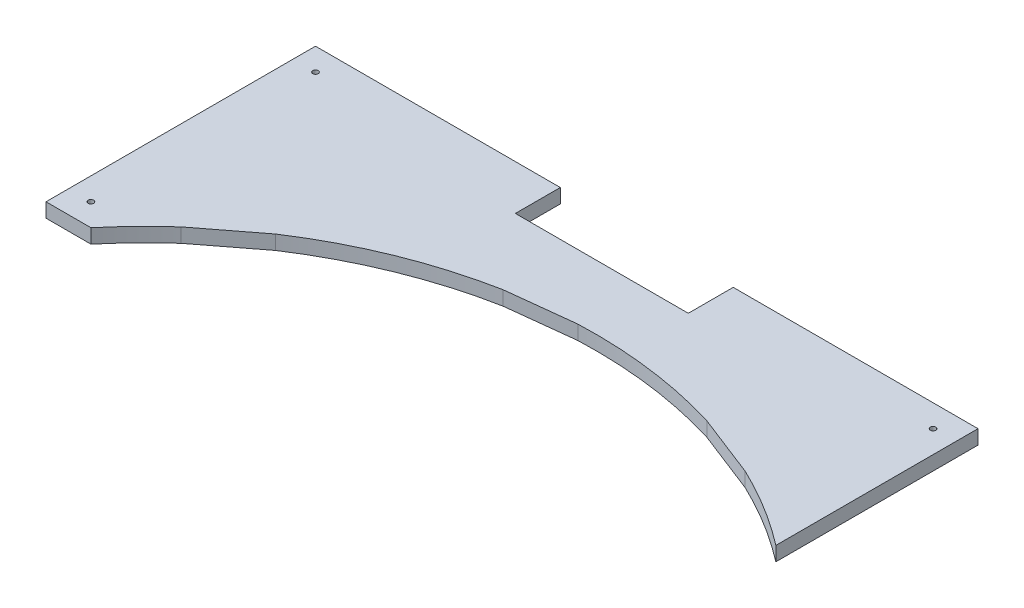
SolidWorks part; units mm, degrees
material "Balsa"
ref_plane "Front Plane" through (0, 0, 0) normal (0, 0, 1) x (1, 0, 0)
ref_plane "Top Plane" through (0, 0, 0) normal (0, 1, 0) x (1, 0, 0)
ref_plane "Right Plane" through (0, 0, 0) normal (1, 0, 0) x (0, 0, -1)
sketch "Sketch1" plane through (0, 0, 0) normal (0, 1, 0) x (1, 0, 0)
  line L0 (20, 0) -> (0, 0)
  line L5 (0, 0) -> (0, 120)
  line L6 (0, 120) -> (295, 120)
  line L7 (295, 120) -> (295, 30)
  line L17 (39.7609, 20.3984) -> (63.5533, 38.6789)
  line L18 (135.6372, 67.8391) -> (165.645, 71.2503)
  line L19 (231.6087, 62.6625) -> (259.6066, 51.7472)
  arc A0 (20, 0) -> (39.7609, 20.3984) centre (173.1663, -128.6082) cw
  arc A1 (63.5533, 38.6789) -> (135.6372, 67.8391) centre (173.1663, -128.6082) cw
  arc A2 (165.645, 71.2503) -> (231.6087, 62.6625) centre (173.1663, -128.6082) cw
  arc A3 (259.6066, 51.7472) -> (295, 30) centre (173.1663, -128.6082) cw
  circle A4 centre (10, 110) radius 1.225
  circle A5 centre (10, 10) radius 1.225
  circle A6 centre (285, 110) radius 1.225
  dimension "D5" = 200
  dimension "D8" = 2.45
  dimension "D11" = 2.45
  dimension "D14" = 2.45
  dimension "D1" = 295
  dimension "D2" = 20
  dimension "D3" = 120
  dimension "D4" = 90
  dimension "D6" = 10
  dimension "D7" = 10
  dimension "D9" = 10
  dimension "D10" = 10
  dimension "D12" = 10
  dimension "D13" = 10
extrude "Boss-Extrude1" add sketch "Sketch1" along normal blind 6.35
sketch "Sketch3" plane through (0, 6.35, 0) normal (0, 1, 0) x (1, 0, 0)
  line L0 (147.5, 120) -> (147.5, 69.1877) construction
  line L5 (295, 120) -> (0, 120) construction
  line L6 (135.6372, 67.8391) -> (165.645, 71.2503) construction
  line L7 (147.5, 100) -> (147.5, 120) construction
  line L8 (109, 120) -> (186, 120)
  line L9 (109, 120) -> (109, 100)
  line L10 (109, 100) -> (186, 100)
  line L11 (186, 120) -> (186, 100)
  dimension "D1" = 20
  dimension "D2" = 77
extrude "Cut-Extrude7" cut sketch "Sketch3" against normal through all
